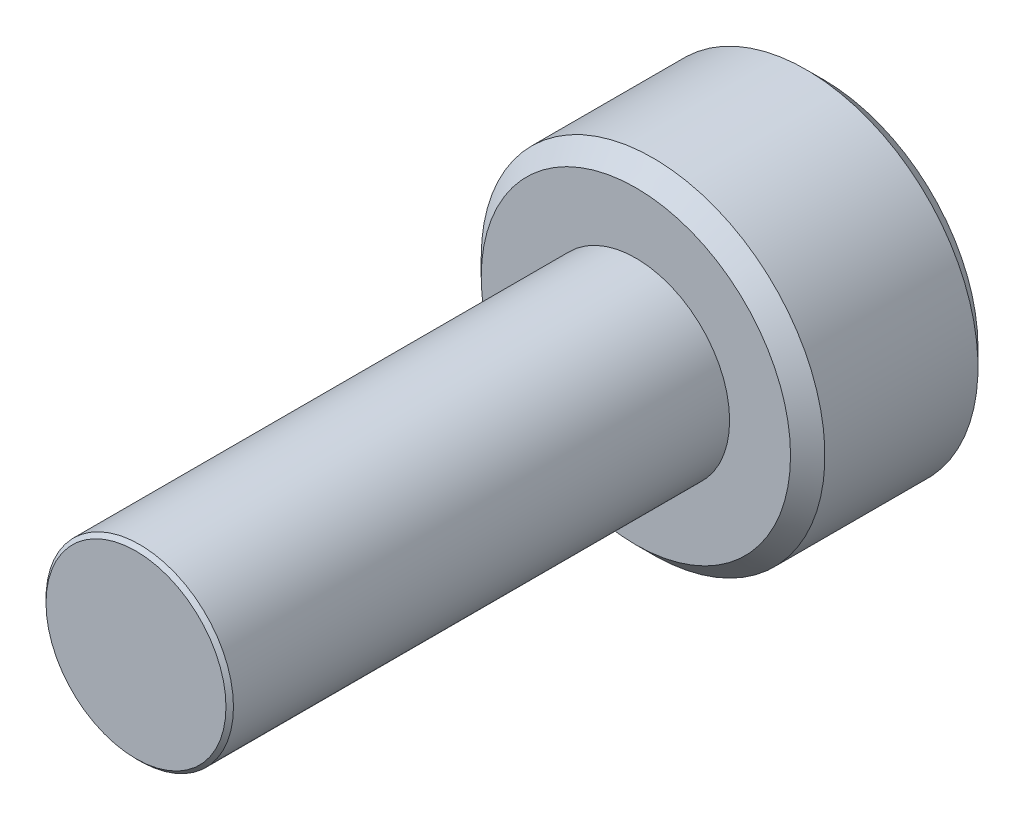
SolidWorks part; units mm, degrees
ref_plane "Front Plane" through (0, 0, 0) normal (0, 0, 1) x (1, 0, 0)
ref_plane "Top Plane" through (0, 0, 0) normal (0, 1, 0) x (1, 0, 0)
ref_plane "Right Plane" through (0, 0, 0) normal (1, 0, 0) x (0, 0, -1)
sketch "Sketch1" plane through (0, 0, 0) normal (0, 0, 1) x (1, 0, 0)
  circle A0 centre (0, 0) radius 1.5
  dimension "OD" = 3
extrude "Extrude1" add sketch "Sketch1" against normal blind 8
sketch "Sketch2" plane through (0, 0, 0) normal (0, 0, 1) x (1, 0, 0)
  circle A0 centre (0, 0) radius 1.5 construction
  circle A1 centre (0, 0) radius 1.5
curve "Helix/Spiral1" pitch 0.5 height 8.5 radius 1.5 centre (0, 0, 0) axis (0, 0, -1) start towards (0, 1, 0) parameters "pitch"=0.5
sketch "Sketch3" plane through (0, 0, 0) normal (1, 0, 0) x (0, 0, -1)
  line L0 (-0.4375, 1.5) -> (-0.25, 1.1752)
  line L1 (-0.25, 1.1752) -> (-0.1875, 1.1752)
  line L2 (-0.1875, 1.1752) -> (0, 1.5)
  line L3 (-0.4375, 1.5) -> (0, 1.5)
  line L4 (-0.2187, 1.5) -> (-0.2188, 1.1752) construction
  line L5 (-0.3438, 1.3376) -> (-0.0938, 1.3376) construction
  line L6 (0, 1.5) -> (0, -1.5) construction
  dimension "D1" = 0.0625
  dimension "D2" = 0.25
  dimension "D3" = 60
sweep "Cut-Sweep1" cut profiles "Sketch3" path "Helix/Spiral1" align with end faces yes
sketch "Sketch4" plane through (0, 0, 0) normal (1, 0, 0) x (0, 0, -1)
  line L0 (0.4053, 1.5) -> (0, 0.9212)
  line L1 (0, 0.9212) -> (0, 1.5)
  line L2 (0.4053, 1.5) -> (0, 1.5)
  line L3 (-0.4375, 1.5) -> (0, 1.5) construction
  line L4 (0, 0) -> (7.0209, 0) construction
  dimension "D1" = 55
  dimension "D2" = 0.254
revolve "Cut-Revolve1" cut sketch "Sketch4" angle 360 about L4
sketch "Sketch6" plane through (0, 0, -8) normal (0, 0, -1) x (-1, 0, 0)
  circle A0 centre (0, 0) radius 2.75
  dimension "head dia" = 5.5
extrude "Extrude2" add sketch "Sketch6" along normal blind 3
sketch "Sketch7" plane through (0, 0, -11) normal (0, 0, -1) x (-1, 0, 0)
  line L1 (0, 1.4434) -> (-1.25, 0.7217)
  line L2 (-1.25, 0.7217) -> (-1.25, -0.7217)
  line L3 (-1.25, -0.7217) -> (0, -1.4434)
  line L4 (0, -1.4434) -> (1.25, -0.7217)
  line L5 (1.25, -0.7217) -> (1.25, 0.7217)
  line L6 (1.25, 0.7217) -> (0, 1.4434)
  circle A0 centre (0, 0) radius 1.25 construction
  dimension "hex dia" = 2.5
extrude "Cut-Extrude1" cut sketch "Sketch7" against normal blind 1.875
sketch "Sketch8" plane through (0, 0, -11) normal (0, 0, -1) x (-1, 0, 0)
  circle A0 centre (0, 0) radius 1.4434
extrude "Cut-Extrude2" cut sketch "Sketch8" against normal through all draft 45
chamfer "Chamfer1" distance 0.275 angle 45 2 edges at (-2.75, 0, -11) (-2.75, 0, -8)
sketch "Sketch10" plane through (0, 0, -8) normal (0, 0, 1) x (1, 0, 0)
  circle A1 centre (0, 0) radius 1.5
  circle A2 centre (0, 0) radius 1.5
  dimension "D1" = 0
ref_plane "Plane1" through (0, 0, 0) normal (0, 0, 1) x (1, 0, 0)
extrude "partial thread" add sketch "Sketch10" along normal up to surface (8 mm away) separate body up to plane "Plane1"
chamfer "Chamfer2" distance 0.06 angle 45 1 edges at (1.5, 0, 0)
combine bodies "Combine1" operation type add bodies to combine 107 108
sketch "Sketch9" plane through (0, 0, 0) normal (1, 0, 0) x (0, 0, -1)
  line L0 (0, 1.5) -> (0, -1.5) construction
  line L1 (1.25, 1.5) -> (1.25, -1.5) construction
  dimension "D1" = 1.25
equation "\"D3@Helix/Spiral1\" = \"screw length@Extrude1\"+\"pitch@Helix/Spiral1\""
equation "\"D1@Sketch3\" = \"pitch@Helix/Spiral1\"*.125"
equation "\"D2@Sketch3\" = \"pitch@Helix/Spiral1\"*.5"
equation "\"D1@Cut-Extrude1\" = \"hex dia@Sketch7\"*.75"
equation "\"D1@Chamfer1\" = \"head dia@Sketch6\"*.05"
equation "\"D1@Sketch9\" = \"pitch@Helix/Spiral1\"*2.5"
equation "\"D1@Chamfer2\"=\"OD@Sketch1\"*.02"
